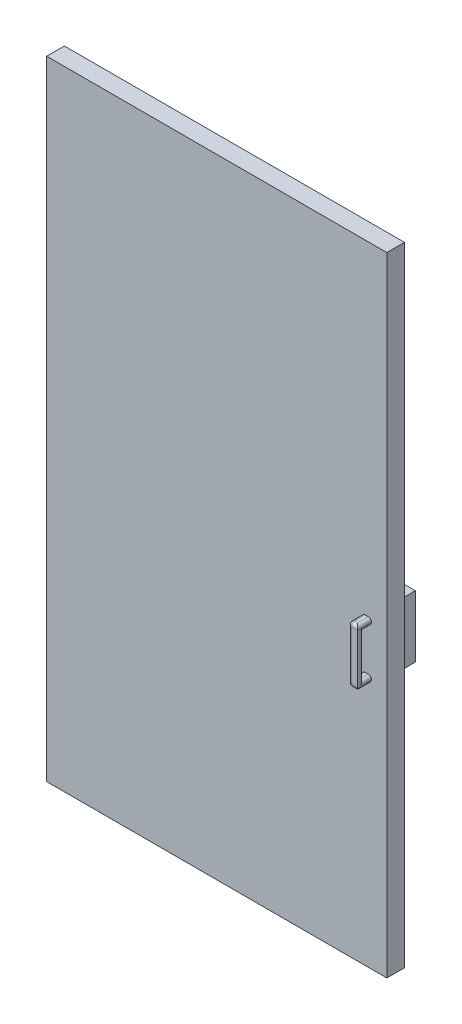
SolidWorks part; units mm, degrees
ref_plane "Front Plane" through (0, 0, 0) normal (0, 0, 1) x (1, 0, 0)
ref_plane "Top Plane" through (0, 0, 0) normal (0, 1, 0) x (1, 0, 0)
ref_plane "Right Plane" through (0, 0, 0) normal (1, 0, 0) x (0, 0, -1)
sketch "Sketch1" plane through (0, 0, 0) normal (0, 0, 1) x (1, 0, 0)
  line L0 (0, 0) -> (0, 18.7953) construction
  line L1 (0, 0) -> (0, 446.2018)
  line L2 (0, 446.2018) -> (-1100, 446.2018)
  line L3 (-1100, 446.2018) -> (-1100, -1585.7982)
  line L4 (-1100, -1585.7982) -> (0, -1585.7982)
  line L5 (0, -1585.7982) -> (0, 0)
  line L7 (-130, -553.7982) -> (-100, -553.7982)
  line L8 (-130, -553.7982) -> (-130, -735.7982)
  line L9 (-130, -735.7982) -> (-100, -735.7982)
  line L10 (-100, -553.7982) -> (-100, -735.7982)
  line L11 (-130, -553.7982) -> (-100, -735.7982) construction
  line L12 (-130, -735.7982) -> (-100, -553.7982) construction
  point P9 (-115, -644.7982)
  dimension "D1" = 1100
  dimension "D2" = 2032
  dimension "D3" = 30
  dimension "D4" = 182
  dimension "D5" = 850
  dimension "D6" = 100
extrude "Boss-Extrude2" add sketch "Sketch1" along normal blind 57.15 contours L3 L4 L5 L1 L2
sketch "Sketch4" plane through (0, 0, 57.15) normal (0, 0, 1) x (1, 0, 0)
  line L0 (-50, 0) -> (-50, -1857.8255) construction
  line L1 (-1100, -1585.7982) -> (0, -1585.7982) construction
  line L2 (-80, -603.7982) -> (-50, -603.7982)
  line L3 (-80, -603.7982) -> (-80, -785.7982)
  line L4 (-80, -785.7982) -> (-50, -785.7982)
  line L5 (-50, -603.7982) -> (-50, -785.7982)
  line L6 (-80, -603.7982) -> (-50, -785.7982) construction
  line L7 (-80, -785.7982) -> (-50, -603.7982) construction
  point P1 (-65, -694.7982)
  dimension "D1" = 50
  dimension "D2" = 30
  dimension "D3" = 182
  dimension "D4" = 800
extrude "Boss-Extrude3" add sketch "Sketch4" along normal blind 44
sketch "Sketch5" plane through (-80, 0, 0) normal (-1, 0, 0) x (0, 0, 1)
  line L0 (57.15, -603.7982) -> (57.15, -785.7982)
  line L1 (57.15, -624.7982) -> (83.15, -624.7982)
  line L2 (83.15, -624.7982) -> (83.15, -764.7982)
  line L3 (83.15, -764.7982) -> (57.15, -764.7982)
  line L4 (57.15, -624.7982) -> (57.15, -764.7982)
  line L5 (101.15, -785.7982) -> (57.15, -785.7982) construction
  dimension "D1" = 140
  dimension "D2" = 21
  dimension "D3" = 26
extrude "Cut-Extrude1" cut sketch "Sketch5" against normal blind 44 contours L3 L2 L1 L0 region at (-80, -694.7982, 70.15)
fillet "Fillet1" radius 10 13 edges at (-80, -694.7982, 83.15) (-80, -603.7982, 79.15) (-80, -624.7982, 70.15) (-50, -603.7982, 79.15) (-50, -624.7982, 70.15) (-50, -694.7982, 83.15) (-50, -764.7982, 70.15) (-50, -785.7982, 79.15) (-80, -785.7982, 79.15) (-80, -764.7982, 70.15) (-80, -694.7982, 101.15) (-65, -785.7982, 101.15) (-65, -603.7982, 101.15)
sketch "Sketch6" plane through (0, 0, 0) normal (0, 0, -1) x (-1, 0, 0)
  line L1 (65, -612.0487) -> (135, -612.0487)
  line L2 (65, -612.0487) -> (65, -812.0487)
  line L3 (65, -812.0487) -> (135, -812.0487)
  line L4 (135, -612.0487) -> (135, -812.0487)
  line L5 (0, -1585.7982) -> (0, 446.2018) construction
  point P4 (100, -812.0487)
  dimension "D1" = 100
  dimension "D2" = 70
  dimension "D3" = 200
extrude "Boss-Extrude4" add sketch "Sketch6" along normal blind 100
sketch "Sketch8" plane through (-65, 0, 0) normal (1, 0, 0) x (0, 0, -1)
  line L0 (0, -627.9356) -> (58.5582, -627.9356)
  line L1 (0, -1585.7982) -> (0, 446.2018) construction
  line L2 (58.5582, -627.9356) -> (58.5582, -786.7631)
  line L3 (58.5582, -786.7631) -> (0, -786.7631)
  line L4 (0, -786.7631) -> (0, -627.9356)
extrude "Cut-Extrude3" cut sketch "Sketch8" against normal up to surface (70 mm away) up to face at (-135, -712.0487, -50)
